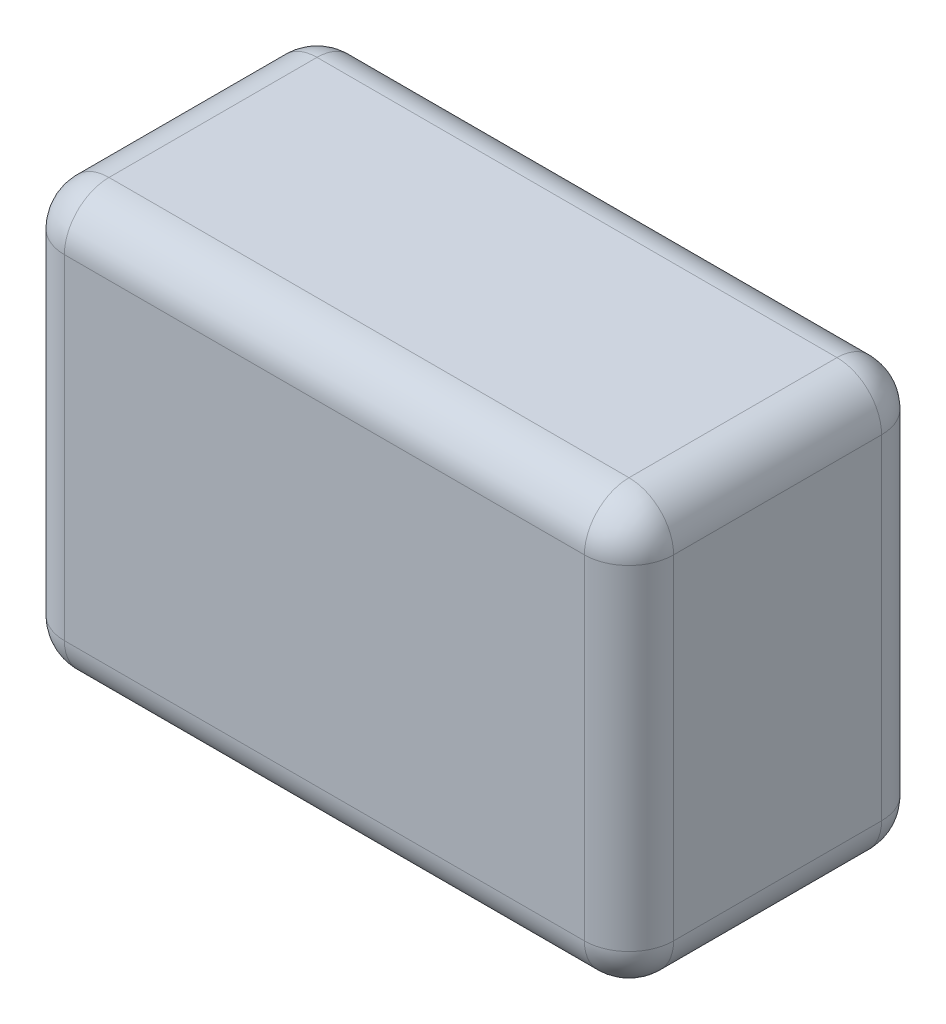
SolidWorks part; units mm, degrees
ref_plane "Front Plane" through (0, 0, 0) normal (0, 0, 1) x (1, 0, 0)
ref_plane "Top Plane" through (0, 0, 0) normal (0, 1, 0) x (1, 0, 0)
ref_plane "Right Plane" through (0, 0, 0) normal (1, 0, 0) x (0, 0, -1)
sketch "Sketch1" plane through (0, 0, 0) normal (0, 1, 0) x (1, 0, 0)
  line L1 (0, 0) -> (82, 0)
  line L2 (0, 0) -> (0, -40)
  line L3 (0, -40) -> (82, -40)
  line L4 (82, 0) -> (82, -40)
  dimension "D1" = 82
  dimension "D2" = 40
extrude "Boss-Extrude1" add sketch "Sketch1" along normal blind 57
fillet "Fillet1" radius 6 12 edges at (0, 28.5, 40) (82, 28.5, 40) (82, 28.5, 0) (0, 28.5, 0) (41, 57, 0) (82, 57, 20) (41, 57, 40) (0, 57, 20) (41, 0, 0) (82, 0, 20) (41, 0, 40) (0, 0, 20)
